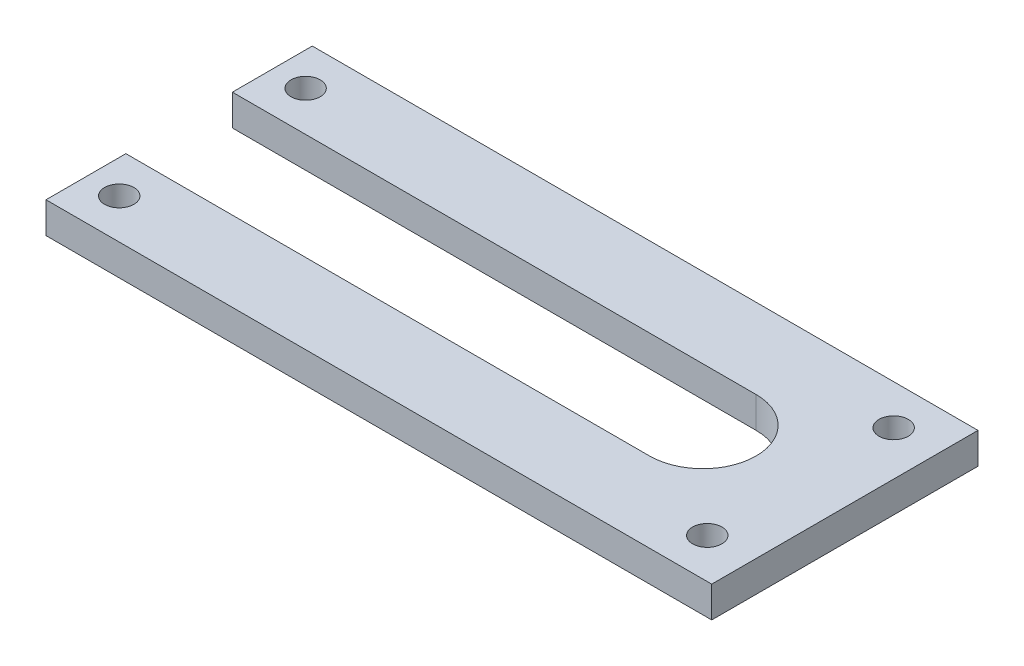
SolidWorks part; units mm, degrees
ref_plane "Piano frontale" through (0, 0, 0) normal (0, 0, 1) x (1, 0, 0)
ref_plane "Piano superiore" through (0, 0, 0) normal (0, 1, 0) x (1, 0, 0)
ref_plane "Piano destro" through (0, 0, 0) normal (1, 0, 0) x (0, 0, -1)
sketch "Schizzo1" plane through (0, 0, 0) normal (0, 0, 1) x (1, 0, 0)
  line L0 (657.3639, 1138.1786) -> (3286.8194, 1138.1786) construction
  line L1 (0, 0) -> (150, 0)
  line L2 (150, 0) -> (150, 7)
  line L3 (150, 7) -> (0, 7)
  line L4 (0, 7) -> (0, 0)
  dimension "D1" = 150
  dimension "D2" = 7
extrude "Estrusione-Estrusione1" add sketch "Schizzo1" against normal blind 80
sketch "Schizzo2" plane through (0, 0, 0) normal (0, 1, 0) x (1, 0, 0)
  line L0 (85.8333, 29.5335) -> (333.8638, 29.5335) construction
  line L1 (85.8333, 102.5) -> (429.1667, 102.5) construction
  line L2 (0, 0) -> (0, 18)
  line L3 (0, 80) -> (0, 0) construction
  line L4 (0, 60) -> (150, 60)
  line L5 (150, 80) -> (150, 0) construction
  line L6 (150, 60) -> (150, 0)
  line L7 (150, 0) -> (0, 0)
  line L8 (0, 30) -> (150, 30) construction
  line L9 (0, 18) -> (118, 18)
  line L10 (0, 42) -> (118, 42)
  line L11 (118, 46.6294) -> (118, -4.7929) construction
  line L12 (0, 18) -> (150, 18) construction
  line L13 (0, 42) -> (150, 42) construction
  line L14 (140, 63.3143) -> (140, -10.7232) construction
  line L15 (0, 42) -> (0, 60)
  line L16 (-28.7018, 97.8291) -> (174.8691, 97.8291)
  line L17 (-28.7018, 97.8291) -> (-28.7018, -40.845)
  line L18 (-28.7018, -40.845) -> (174.8691, -40.845)
  line L19 (174.8691, 97.8291) -> (174.8691, -40.845)
  line L20 (140, 51) -> (-34.5064, 51) construction
  arc A0 (118, 18) -> (118, 42) centre (118, 30) ccw
  circle A1 centre (140, 51) radius 3.3
  circle A2 centre (140, 9) radius 3.3
  circle A3 centre (7.5, 51) radius 3.3
  circle A4 centre (7.5, 9) radius 3.3
  dimension "D3" = 32
  dimension "D6" = 6.6
  dimension "D7" = 6.6
  dimension "D1" = 60
  dimension "D2" = 24
  dimension "D4" = 10
  dimension "D5" = 9
  dimension "D8" = 7.5
extrude "Taglio-Estrusione1" cut sketch "Schizzo2" along normal through all contours L19 L16 L17 L18 L9 A0 L10 L15 L4 L6 L7 L2 | A2 | A1 | A4 | A3 region at (71.0278, 0, -28.0901)
